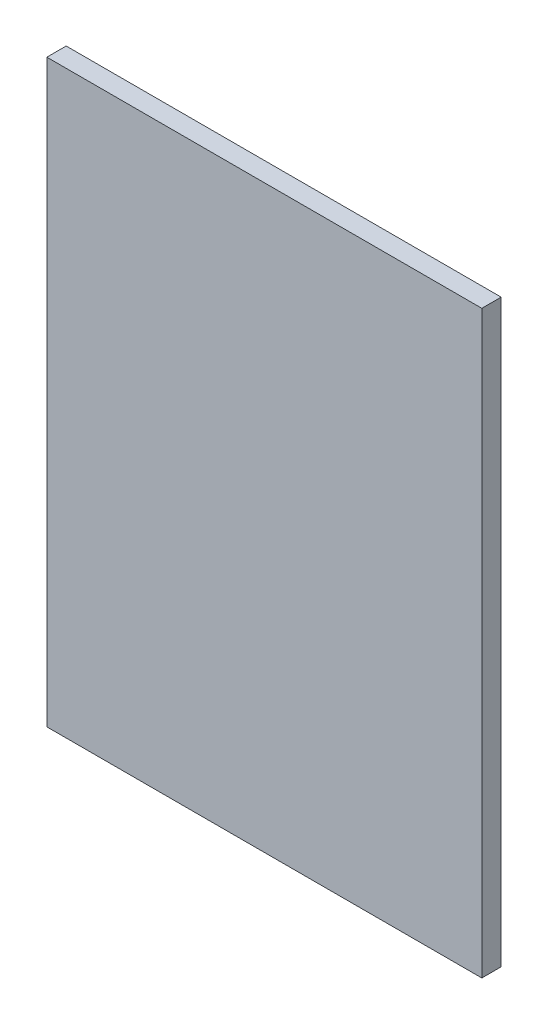
SolidWorks part; units mm, degrees
ref_plane "Front Plane" through (0, 0, 0) normal (0, 0, 1) x (1, 0, 0)
ref_plane "Top Plane" through (0, 0, 0) normal (0, 1, 0) x (1, 0, 0)
ref_plane "Right Plane" through (0, 0, 0) normal (1, 0, 0) x (0, 0, -1)
sketch "Sketch1" plane through (0, 0, 0) normal (0, 0, 1) x (1, 0, 0)
  line L1 (-112.5, -150) -> (112.5, -150)
  line L2 (-112.5, -150) -> (-112.5, 150)
  line L3 (-112.5, 150) -> (112.5, 150)
  line L4 (112.5, -150) -> (112.5, 150)
  line L5 (-112.5, -150) -> (112.5, 150) construction
  line L6 (-112.5, 150) -> (112.5, -150) construction
  point P0 (0, 0)
  dimension "D1" = 225
  dimension "D2" = 300
extrude "Boss-Extrude1" add sketch "Sketch1" along normal blind 10
equation "\"PCWidth\"= 172mm"
equation "\"PCLength\"= 320mm"
equation "\"PCHeight\"= 242mm"
equation "\"WallThickness\"= 10mm"
equation "\"ThermoBarrierThickness\"= 3mm"
equation "\"HotSideGap\"= 50mm"
equation "\"PCClearance\"= 25mm"
equation "\"D2@Sketch1\"=\"RadiatorHeight\" + \"PCClearance\""
equation "\"D1@Sketch1\"=\"PCWidth\" + \"ThermoBarrierThickness\" + \"HotSideGap\""
equation "\"D1@Boss-Extrude1\"=\"WallThickness\""
equation "\"RadiatorHeight\"= 275mm"
